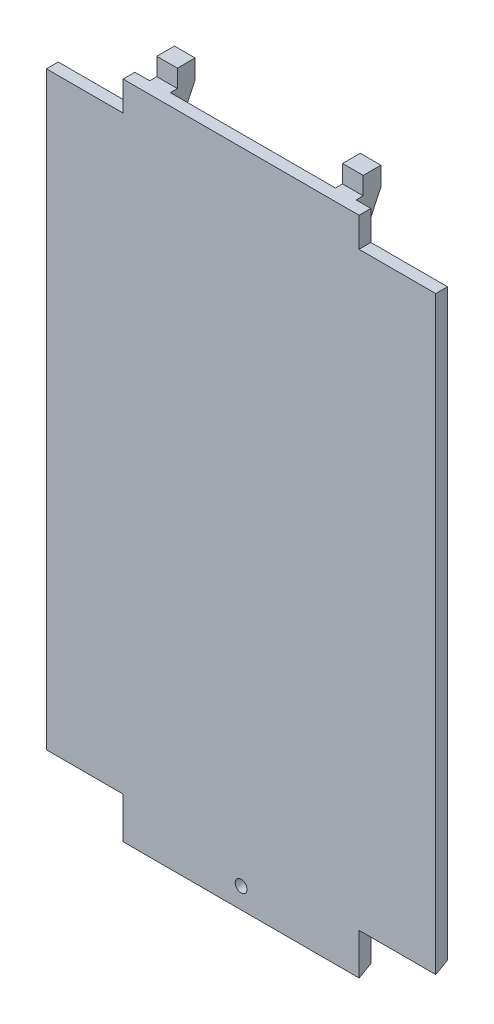
SolidWorks part; units mm, degrees
ref_plane "前基準面" through (0, 0, 0) normal (0, 0, 1) x (1, 0, 0)
ref_plane "上基準面" through (0, 0, 0) normal (0, 1, 0) x (1, 0, 0)
ref_plane "右基準面" through (0, 0, 0) normal (1, 0, 0) x (0, 0, -1)
sketch "草圖1" plane through (0, 0, 0) normal (0, 0, 1) x (1, 0, 0)
  line L1 (0, 0) -> (40, 0)
  line L2 (0, 0) -> (0, 112)
  line L3 (0, 112) -> (40, 112)
  line L4 (40, 0) -> (40, 112)
extrude "填料-伸長1" add sketch "草圖1" along normal blind 3
sketch "草圖2" plane through (0, 0, 0) normal (0, 0, 1) x (1, 0, 0)
  circle A0 centre (20, 3.5) radius 1
extrude "除料-伸長1" cut sketch "草圖2" along normal blind 3
sketch "草圖3" plane through (0, 0, 0) normal (0, 0, 1) x (1, 0, 0)
  line L1 (34, 115) -> (37.5, 115)
  line L2 (34, 115) -> (34, 105)
  line L3 (34, 105) -> (37.5, 105)
  line L4 (37.5, 115) -> (37.5, 105)
  line L5 (6, 115) -> (2.5, 115)
  line L6 (6, 115) -> (6, 105)
  line L7 (6, 105) -> (2.5, 105)
  line L8 (2.5, 115) -> (2.5, 105)
extrude "填料-伸長2" add sketch "草圖3" against normal blind 3.2
chamfer "導角1" distance 6.8 angle 25 2 edges at (35.75, 105, -3.2) (4.25, 105, -3.2) first distance on face at (35.75, 110, -3.2) first distance on face at (4.25, 110, -3.2)
sketch "草圖4" plane through (0, 0, 0) normal (0, 0, 1) x (1, 0, 0)
  line L1 (53, 7) -> (-13, 7)
  line L2 (53, 7) -> (53, 107)
  line L3 (53, 107) -> (-13, 107)
  line L4 (-13, 7) -> (-13, 107)
  point P4 (0, 0)
  point P5 (0, 0)
  point P6 (0, 0)
  point P7 (0, 0)
extrude "填料-伸長3" add sketch "草圖4" along normal blind 3
sketch "草圖5" plane through (0, 0, 0) normal (0, 0, 1) x (1, 0, 0)
  line L1 (-3, 112) -> (39.2596, 112)
  line L2 (-3, 112) -> (-3, 115.1657)
  line L3 (-3, 115.1657) -> (39.2596, 115.1657)
  line L4 (39.2596, 112) -> (39.2596, 115.1657)
  point P4 (0, 0)
extrude "除料-伸長2" cut sketch "草圖5" against normal blind 0.2
chamfer "導角3" distance 1 angle 45 11 edges at (40, 3.5, 0) (53, 57, 0) (46.5, 107, 0) (40, 109.5, 0) (38.75, 112, 0) (20, 112, 0) (1.25, 112, 0) (0, 109.5, 0) (-6.5, 107, 0) (-13, 57, 0) (0, 3.5, 0)
chamfer "導角4" distance 1.7 angle 60 3 edges at (-5.5, 7, 0) (45.5, 7, 0) (20, 0, 0) first distance on face at (20, 76.9, 0)
